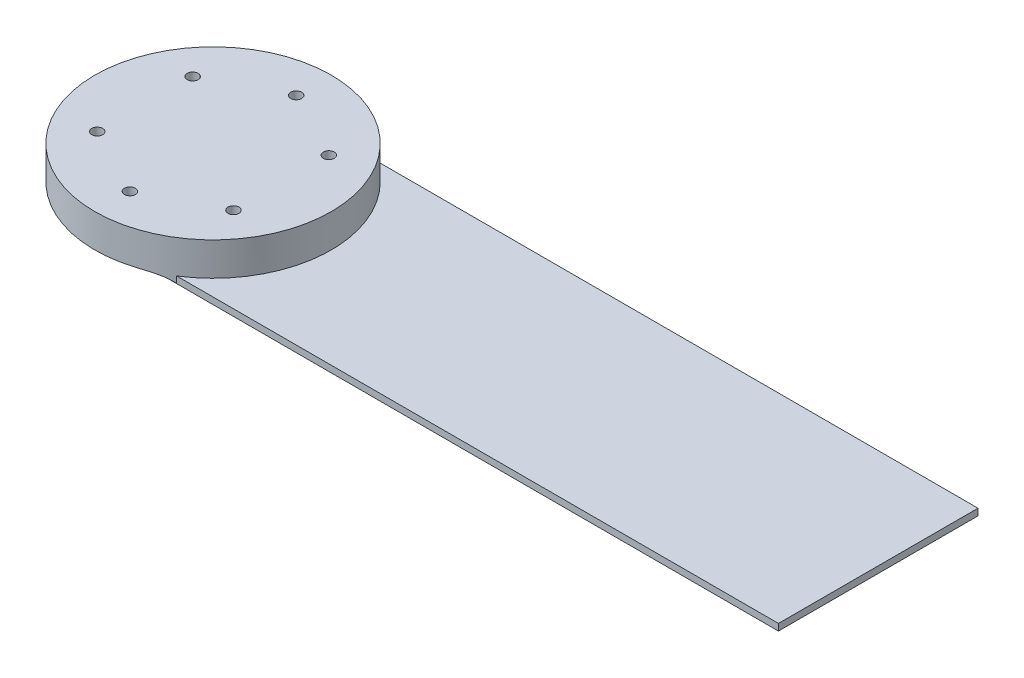
SolidWorks part; units mm, degrees
ref_plane "Front Plane" through (0, 0, 0) normal (0, 0, 1) x (1, 0, 0)
ref_plane "Top Plane" through (0, 0, 0) normal (0, 1, 0) x (1, 0, 0)
ref_plane "Right Plane" through (0, 0, 0) normal (1, 0, 0) x (0, 0, -1)
sketch "Sketch2" plane through (0, 0, 0) normal (0, 1, 0) x (1, 0, 0)
  line L0 (0, 0) -> (200, 0)
  line L1 (0, -60) -> (200, -60)
  line L2 (200, -60) -> (200, 0)
  arc A0 (0, 0) -> (0, -60) centre (0, -30) ccw
  dimension "D1" = 200
  dimension "D2" = 60
extrude "Boss-Extrude1" add sketch "Sketch2" along normal blind 2
sketch "Sketch3" plane through (0, 2, 0) normal (0, 1, 0) x (1, 0, 0)
  circle A0 centre (0, -30) radius 35.55
  dimension "D1" = 71.1
extrude "Boss-Extrude2" add sketch "Sketch3" along normal blind 10
fillet "Fillet1" radius 5 3 edges at (9.5368, 2, 0) (9.5368, 2, 60) (-30, 2, 30)
sketch "Sketch4" plane through (0, 12, 0) normal (0, 1, 0) x (1, 0, 0)
  line L0 (0, -30) -> (-25, -30) construction
  line L1 (0, -30) -> (-20.4788, -15.6606) construction
  circle A1 centre (0, -5) radius 1.65
  circle A2 centre (0, -55) radius 1.65
  circle A3 centre (-20.4788, -15.6606) radius 1.65
  circle A4 centre (-20.4788, -44.3394) radius 1.65
  circle A5 centre (20.4788, -15.6606) radius 1.65
  circle A6 centre (20.4788, -44.3394) radius 1.65
  dimension "D2" = 3.3
  dimension "D3" = 35
extrude "Cut-Extrude1" cut sketch "Sketch4" against normal blind 19
